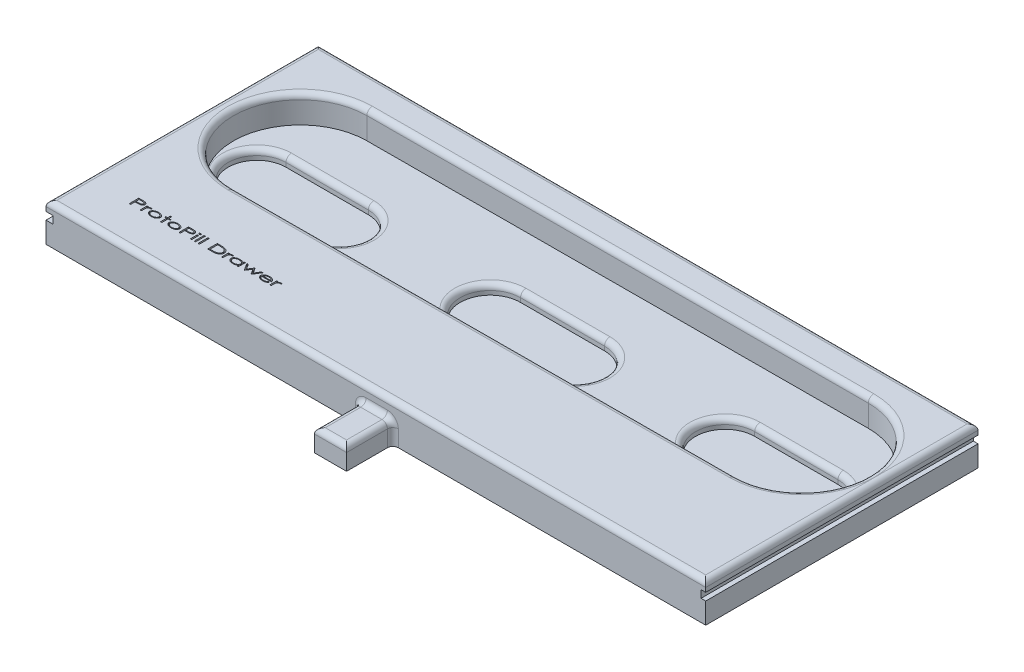
SolidWorks part; units mm, degrees
ref_plane "Front Plane" through (0, 0, 0) normal (0, 0, 1) x (1, 0, 0)
ref_plane "Top Plane" through (0, 0, 0) normal (0, 1, 0) x (1, 0, 0)
ref_plane "Right Plane" through (0, 0, 0) normal (1, 0, 0) x (0, 0, -1)
sketch "Sketch1" plane through (0, 0, 0) normal (0, 1, 0) x (1, 0, 0)
  line L2 (2.2154, -28.3198) -> (244.3174, -28.3198)
  line L4 (244.3174, 64.6802) -> (2.2154, 64.6802)
  line L6 (244.3174, 64.6802) -> (244.3174, -28.3198)
  line L7 (2.2154, 64.6802) -> (2.2154, -28.3198)
  dimension "D2" = 93
extrude "Boss-Extrude1" add sketch "Sketch1" along normal blind 14
sketch "Sketch3" plane through (0, 14, 0) normal (0, 1, 0) x (1, 0, 0)
  line L0 (37.1381, -19.9605) -> (-7.858, -19.9605) construction
  line L2 (37.1381, -19.9605) -> (37.1381, -24.4605) construction
  line L4 (37.1381, -19.9605) -> (123.1941, -19.9579) construction
  line L5 (123.6473, -19.9605) -> (210.1566, -19.9605) construction
  line L6 (210.1566, -19.9605) -> (210.1566, -24.4605) construction
  line L7 (123.6473, -19.9605) -> (123.6473, -24.4605) construction
  line L8 (37.1381, -19.9605) -> (37.1381, 7.1502) construction
  line L9 (123.6473, -19.9605) -> (123.6473, 8.5509) construction
  line L10 (210.1566, -19.9605) -> (210.1566, 7.8884) construction
  line L11 (0.0174, -19.9605) -> (247.1649, -19.9605)
  circle A2 centre (123.7727, -8.9393) radius 11.15
  circle A3 centre (37.3245, -8.6421) radius 11.15
  circle A4 centre (209.8985, -8.6813) radius 11.15
  dimension "D2" = 22.3
  dimension "D3" = 22.3
  dimension "D4" = 22.3
sketch "Sketch2" plane through (0, 0, 28.3198) normal (0, 0, 1) x (1, 0, 0)
  line L0 (0, 10.4529) -> (0, 7.6902)
  line L2 (0, 7.6902) -> (4.6941, 7.6902)
  line L3 (4.6941, 7.6902) -> (4.6941, 10.4529)
  line L5 (4.6941, 10.4529) -> (0, 10.4529)
extrude "Cut-Extrude1" cut sketch "Sketch2" against normal through all
ref_plane "Plane1" through (123.6473, 0, 0) normal (1, 0, 0) x (0, 0, -1)
mirror "Mirror5" about plane through (123.6473, 0, 0) normal (1, 0, 0) of "Cut-Extrude1"
sketch "Sketch7" plane through (0, 0, 28.3198) normal (0, 0, 1) x (1, 0, 0)
  line L0 (123.5912, 14) -> (123.6473, 0) construction
  line L1 (0.0174, 14) -> (247.1649, 14) construction
  line L2 (2.2154, 0) -> (244.3174, 0) construction
  line L3 (123.6473, -7.7) -> (123.6473, 7.7) construction
  line L9 (117.7248, 7.9809) -> (129.5137, 6.0191) construction
  line L10 (117.7248, 6.0191) -> (129.5137, 7.9809) construction
  line L11 (117.7248, 0) -> (129.5137, 0)
  line L12 (117.7248, 0) -> (117.7248, 7.9809)
  line L13 (117.7248, 7.9809) -> (129.5137, 7.9809)
  line L14 (129.5137, 0) -> (129.5137, 7.9809)
  point P8 (123.6193, 7)
extrude "Boss-Extrude2" add sketch "Sketch7" along normal blind 70
sketch "Sketch8" plane through (0, 0, 28.3198) normal (0, 0, 1) x (1, 0, 0)
  line L10 (244.3174, 10.4529) -> (244.3174, 14)
  line L12 (244.3174, 10.4529) -> (244.3174, 14)
  line L14 (244.3174, 14) -> (2.2154, 14)
  line L18 (2.2154, 14) -> (2.2154, 10.4529)
  line L19 (2.2154, 10.4529) -> (4.6941, 10.4529)
  line L20 (4.6941, 10.4529) -> (4.6941, 7.6902)
  line L21 (4.6941, 7.6902) -> (2.2154, 7.6902)
  line L22 (2.2154, 7.6902) -> (2.2154, 0)
  line L23 (2.2154, 0) -> (117.7248, 0)
  line L24 (117.7248, 0) -> (117.7248, 7.9809)
  line L30 (117.7248, 7.9809) -> (129.5137, 7.9809)
  line L31 (117.7248, 7.9809) -> (129.5137, 7.9809)
  line L34 (2.2154, 14) -> (2.2154, 10.4529)
  line L35 (2.2154, 10.4529) -> (4.6941, 10.4529)
  line L36 (4.6941, 10.4529) -> (4.6941, 7.6902)
  line L37 (4.6941, 7.6902) -> (2.2154, 7.6902)
  line L38 (2.2154, 7.6902) -> (2.2154, 0)
  line L39 (2.2154, 0) -> (117.7248, 0)
  line L40 (117.7248, 0) -> (117.7248, 7.9809)
  line L48 (129.5137, 7.9809) -> (129.5137, 0)
  line L49 (129.5137, 7.9809) -> (129.5137, 0)
  line L50 (129.5137, 0) -> (244.3174, 0)
  line L51 (129.5137, 0) -> (244.3174, 0)
  line L52 (244.3174, 0) -> (244.3174, 7.6902)
  line L53 (244.3174, 0) -> (244.3174, 7.6902)
  line L54 (244.3174, 7.6902) -> (242.6006, 7.6902)
  line L55 (244.3174, 7.6902) -> (242.6006, 7.6902)
  line L56 (242.6006, 7.6902) -> (242.6006, 10.4529)
  line L57 (242.6006, 7.6902) -> (242.6006, 10.4529)
  line L58 (242.6006, 10.4529) -> (244.3174, 10.4529)
  line L59 (242.6006, 10.4529) -> (244.3174, 10.4529)
  line L60 (244.3174, 14) -> (2.2154, 14)
  dimension "D1" = 0
extrude "Boss-Extrude3" add sketch "Sketch8" along normal blind 53
sketch "Sketch9" plane through (0, 14, 0) normal (0, 1, 0) x (1, 0, 0)
  line L0 (32.277, -18.0846) -> (215.6701, -17.457) construction
  line L3 (32.193, 6.4621) -> (215.5861, 7.0898)
  line L4 (32.361, -42.6314) -> (215.7541, -42.0037)
  arc A0 (32.193, 6.4621) -> (32.361, -42.6314) centre (32.277, -18.0846) ccw
  arc A1 (215.7541, -42.0037) -> (215.5861, 7.0898) centre (215.6701, -17.457) ccw
  point P6 (123.9735, -17.7708)
extrude "Cut-Extrude2" cut sketch "Sketch9" against normal blind 10
sketch "Sketch10" plane through (0, 4, 0) normal (0, 1, 0) x (1, 0, 0)
  line L0 (22.2559, -23.9029) -> (52.4711, -23.9029) construction
  line L1 (22.2559, -13.2713) -> (52.4711, -13.2713)
  line L2 (22.2559, -34.5345) -> (52.4711, -34.5345)
  line L3 (108.2536, -24.2865) -> (139.0697, -24.2865) construction
  line L4 (108.2536, -13.2003) -> (139.0697, -13.2003)
  line L5 (108.2536, -35.3728) -> (139.0697, -35.3728)
  line L6 (193.8044, -23.6865) -> (224.3383, -23.6865) construction
  line L7 (193.8044, -12.8155) -> (224.3383, -12.8155)
  line L8 (193.8044, -34.5575) -> (224.3383, -34.5575)
  arc A0 (22.2559, -13.2713) -> (22.2559, -34.5345) centre (22.2559, -23.9029) ccw
  arc A1 (52.4711, -34.5345) -> (52.4711, -13.2713) centre (52.4711, -23.9029) ccw
  arc A2 (108.2536, -13.2003) -> (108.2536, -35.3728) centre (108.2536, -24.2865) ccw
  arc A3 (139.0697, -35.3728) -> (139.0697, -13.2003) centre (139.0697, -24.2865) ccw
  arc A4 (193.8044, -12.8155) -> (193.8044, -34.5575) centre (193.8044, -23.6865) ccw
  arc A5 (224.3383, -34.5575) -> (224.3383, -12.8155) centre (224.3383, -23.6865) ccw
  point P2 (37.3635, -23.9029)
  point P9 (123.6616, -24.2865)
  point P16 (209.0714, -23.6865)
extrude "Cut-Extrude4" cut sketch "Sketch10" against normal blind 3.5
fillet "Fillet2" radius 2 4 edges at (240.2169, 14, 17.373) (124.0576, 14, 42.3176) (7.7302, 14, 18.1686) (123.8895, 14, -6.776)
fillet "Fillet3" radius 2 12 edges at (235.2093, 4, 23.6865) (209.0714, 4, 34.5575) (182.9335, 4, 23.6865) (150.1559, 4, 24.2865) (123.6616, 4, 35.3728) (97.1674, 4, 24.2865) (63.1027, 4, 23.9029) (37.3635, 4, 34.5345) (11.6243, 4, 23.9029) (209.0714, 4, 12.8155) (123.6616, 4, 13.2003) (37.3635, 4, 13.2713)
sketch "Sketch11" plane through (0, 14, 0) normal (0, 1, 0) x (1, 0, 0)
  line L0 (2.2154, 18.6064) -> (244.3174, 18.6064)
  line L1 (2.2154, 64.6802) -> (2.2154, -81.3198) construction
  line L2 (244.3174, -81.3198) -> (244.3174, 64.6802) construction
  line L3 (244.3174, 18.6064) -> (244.3174, 64.6802)
  line L4 (244.3174, 64.6802) -> (2.2154, 64.6802)
  line L5 (2.2154, 64.6802) -> (2.2154, 18.6064)
extrude "Cut-Extrude5" cut sketch "Sketch11" against normal through all
fillet "Fillet4" radius 2 10 edges at (117.7248, 3.9904, 81.3198) (129.5137, 3.9904, 81.3198) (123.6193, 7.9809, 98.3198) (117.7248, 7.9809, 89.8198) (123.6193, 7.9809, 81.3198) (129.5137, 7.9809, 89.8198) (244.3174, 14, 31.3567) (123.2664, 14, 81.3198) (2.2154, 14, 31.3567) (123.2664, 14, -18.6064)
sketch "Sketch12" plane through (0, 0, 0) normal (0, -1, 0) x (1, 0, 0)
  circle A0 centre (79.2049, -2.6546) radius 3.025
  circle A2 centre (79.2049, 6.3419) radius 3.025
  circle A10 centre (169.8585, 5.9307) radius 3.025
  circle A11 centre (169.8585, -2.6546) radius 3.025
extrude "Cut-Extrude6" cut sketch "Sketch12" against normal blind 2
sketch "Sketch13" plane through (0, 14, 0) normal (0, 1, 0) x (1, 0, 0)
  text T0 "ProtoPill Drawer" font "Century Gothic" height 3.5
extrude "Cut-Extrude7" cut sketch "Sketch13" against normal blind 2
sketch "Sketch14" plane through (0, 0, 0) normal (0, -1, 0) x (1, 0, 0)
  line L0 (76.1475, 6.1393) -> (79.1725, 12.8178)
  line L1 (79.1725, 12.8178) -> (82.1975, 6.1393)
  line L2 (82.1975, 6.1393) -> (76.1475, 6.1393)
  line L3 (76.1475, -2.8572) -> (79.1725, -9.5356)
  line L4 (79.1725, -9.5356) -> (82.1975, -2.8572)
  line L5 (82.1975, -2.8572) -> (76.1475, -2.8572)
  line L6 (166.8011, 5.7281) -> (169.8261, 12.4066)
  line L7 (169.8261, 12.4066) -> (172.8511, 5.7281)
  line L8 (172.8511, 5.7281) -> (166.8011, 5.7281)
  line L9 (166.8011, -2.8572) -> (169.8261, -9.5356)
  line L10 (169.8261, -9.5356) -> (172.8511, -2.8572)
  line L11 (172.8511, -2.8572) -> (166.8011, -2.8572)
extrude "Cut-Extrude8" cut sketch "Sketch14" against normal blind 2
sketch "Sketch15" plane through (0, 14, 0) normal (0, 1, 0) x (1, 0, 0)
  line L2 (146.7092, -47.8489) -> (134.6091, -54.4141)
  line L3 (146.7092, -47.8489) -> (146.7092, -74.4208)
  line L4 (146.7092, -74.4208) -> (134.6091, -67.8555)
